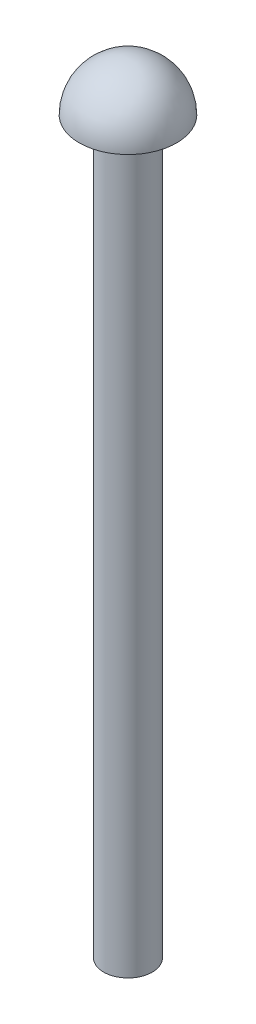
SolidWorks part; units mm, degrees
ref_plane "Front Plane" through (0, 0, 0) normal (0, 0, 1) x (1, 0, 0)
ref_plane "Top Plane" through (0, 0, 0) normal (0, 1, 0) x (1, 0, 0)
ref_plane "Right Plane" through (0, 0, 0) normal (1, 0, 0) x (0, 0, -1)
sketch "Sketch1" plane through (0, 0, 0) normal (0, 1, 0) x (1, 0, 0)
  circle A0 centre (0, 0) radius 1.5
  dimension "D1" = 3
extrude "Boss-Extrude1" add sketch "Sketch1" along normal blind 45
sketch "Sketch4" plane through (0, 45, 0) normal (0, 1, 0) x (1, 0, 0)
  line L0 (0, 3) -> (0, -3)
  circle A0 centre (0, 0) radius 3
revolve "Revolve1" add sketch "Sketch4" angle 180 about L0 region at (2.0739, 45, -2.0739)
